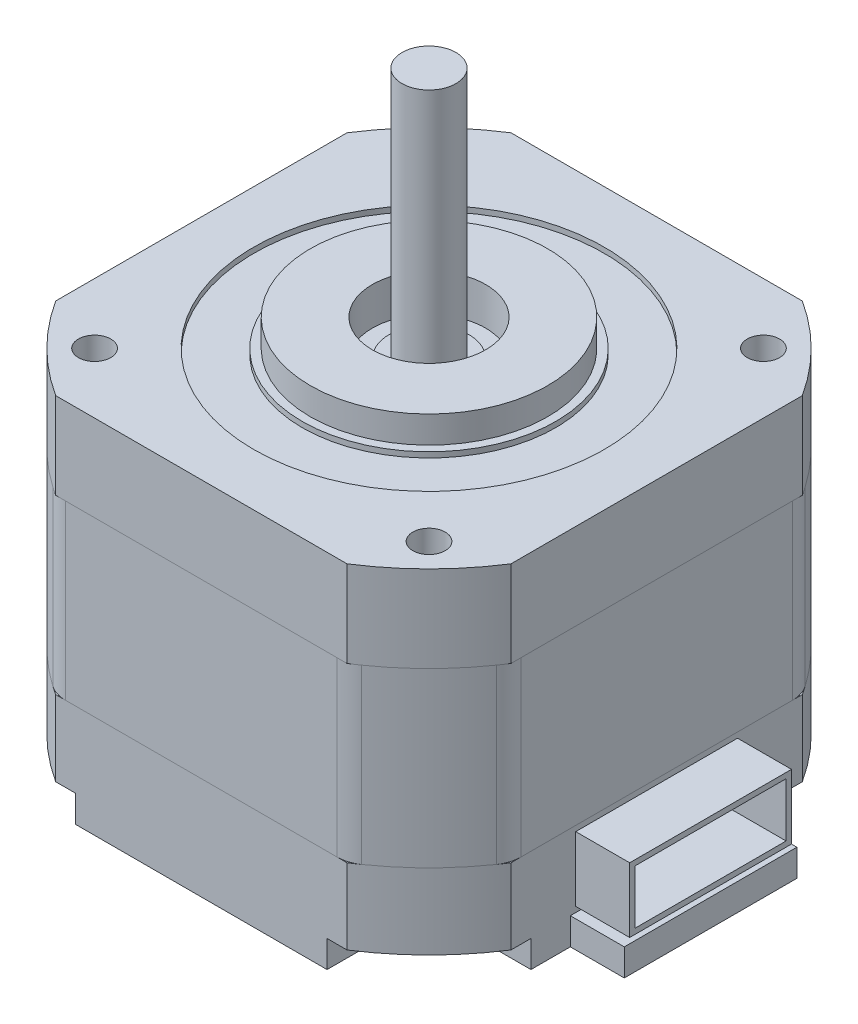
SolidWorks part; units mm, degrees
ref_plane "Alzado" through (0, 0, 0) normal (0, 0, 1) x (1, 0, 0)
ref_plane "Planta" through (0, 0, 0) normal (0, 1, 0) x (1, 0, 0)
ref_plane "Vista lateral" through (0, 0, 0) normal (1, 0, 0) x (0, 0, -1)
sketch "Croquis1" plane through (0, 0, 0) normal (0, 1, 0) x (1, 0, 0)
  line L0 (13.5, 21.1) -> (-13.5, 21.1)
  line L2 (-21.1, 13.5) -> (-21.1, -13.5)
  line L4 (-13.5, -21.1) -> (13.5, -21.1)
  line L6 (21.1, -13.5) -> (21.1, 13.5)
  arc A0 (-13.5, 21.1) -> (-21.1, 13.5) centre (0, 0) ccw
  arc A1 (13.5, 21.1) -> (21.1, 13.5) centre (0, 0) cw
  arc A2 (21.1, -13.5) -> (13.5, -21.1) centre (0, 0) cw
  arc A3 (-21.1, -13.5) -> (-13.5, -21.1) centre (0, 0) ccw
  point P4 (-21.1, 0)
  point P10 (0, 21.1)
  dimension "D2" = 27
  dimension "D1" = 42.2
extrude "Saliente-Extruir1" add sketch "Croquis1" along normal mid plane 16
sketch "Croquis2" plane through (0, 8, 0) normal (0, 1, 0) x (1, 0, 0)
  line L12 (13.5003, 21.101) -> (-13.5003, 21.101)
  line L13 (-21.101, 13.5003) -> (-21.101, -13.5003)
  line L14 (-13.5003, -21.101) -> (13.5003, -21.101)
  line L15 (21.101, -13.5003) -> (21.101, 13.5003)
  line L16 (13.5003, 21.101) -> (-13.5003, 21.101)
  line L17 (-21.101, 13.5003) -> (-21.101, -13.5003)
  line L18 (-13.5003, -21.101) -> (13.5003, -21.101)
  line L19 (21.101, -13.5003) -> (21.101, 13.5003)
  arc A12 (21.101, 13.5003) -> (13.5003, 21.101) centre (0, 0) ccw
  arc A13 (-13.5003, 21.101) -> (-21.101, 13.5003) centre (0, 0) ccw
  arc A14 (-21.101, -13.5003) -> (-13.5003, -21.101) centre (0, 0) ccw
  arc A15 (13.5003, -21.101) -> (21.101, -13.5003) centre (0, 0) ccw
  arc A16 (21.101, 13.5003) -> (13.5003, 21.101) centre (0, 0) ccw
  arc A17 (-13.5003, 21.101) -> (-21.101, 13.5003) centre (0, 0) ccw
  arc A18 (-21.101, -13.5003) -> (-13.5003, -21.101) centre (0, 0) ccw
  arc A19 (13.5003, -21.101) -> (21.101, -13.5003) centre (0, 0) ccw
  dimension "D1" = 0.001
fillet "Redondeo1" radius 3 8 edges at (-21.1, 0, -13.5) (-13.5, 0, -21.1) (13.5, 0, -21.1) (21.1, 0, -13.5) (-21.1, 0, 13.5) (-13.5, 0, 21.1) (13.5, 0, 21.1) (21.1, 0, 13.5)
extrude "Saliente-Extruir2" add sketch "Croquis2" along normal blind 8
sketch "Croquis3" plane through (0, -8, 0) normal (0, -1, 0) x (1, 0, 0)
  line L8 (-13.5003, -21.101) -> (13.5003, -21.101)
  line L9 (-21.101, 13.5003) -> (-21.101, -13.5003)
  line L10 (13.5003, 21.101) -> (-13.5003, 21.101)
  line L11 (21.101, -13.5003) -> (21.101, 13.5003)
  line L12 (-13.5003, -21.101) -> (13.5003, -21.101)
  line L13 (-21.101, 13.5003) -> (-21.101, -13.5003)
  line L14 (13.5003, 21.101) -> (-13.5003, 21.101)
  line L15 (21.101, -13.5003) -> (21.101, 13.5003)
  arc A8 (13.5003, -21.101) -> (21.101, -13.5003) centre (0, 0) ccw
  arc A9 (-21.101, -13.5003) -> (-13.5003, -21.101) centre (0, 0) ccw
  arc A10 (-13.5003, 21.101) -> (-21.101, 13.5003) centre (0, 0) ccw
  arc A11 (21.101, 13.5003) -> (13.5003, 21.101) centre (0, 0) ccw
  arc A12 (13.5003, -21.101) -> (21.101, -13.5003) centre (0, 0) ccw
  arc A13 (-21.101, -13.5003) -> (-13.5003, -21.101) centre (0, 0) ccw
  arc A14 (-13.5003, 21.101) -> (-21.101, 13.5003) centre (0, 0) ccw
  arc A15 (21.101, 13.5003) -> (13.5003, 21.101) centre (0, 0) ccw
  dimension "D1" = 0
extrude "Saliente-Extruir3" add sketch "Croquis3" along normal blind 9.5
sketch "Croquis4" plane through (0, 16, 0) normal (0, 1, 0) x (1, 0, 0)
  line L0 (-15.5, 15.5) -> (-15.5, 21.101) construction
  line L1 (-15.5, 15.5) -> (-21.101, 15.5) construction
  line L2 (-21.101, 13.5003) -> (-21.101, -13.5003) construction
  line L3 (13.5003, 21.101) -> (-13.5003, 21.101) construction
  line L4 (0, 0) -> (0, 21.101) construction
  line L5 (0, 0) -> (-21.101, 0) construction
  circle A0 centre (0, 0) radius 16.25
  circle A1 centre (0, 0) radius 11.75
  circle A2 centre (0, 0) radius 11
  circle A3 centre (-15.5, 15.5) radius 1.5
  circle A7 centre (-15.5, -15.5) radius 1.5
  circle A8 centre (15.5, -15.5) radius 1.5
  circle A9 centre (15.5, 15.5) radius 1.5
  dimension "D1" = 32.5
  dimension "D2" = 23.5
  dimension "D3" = 22
  dimension "D4" = 3
  dimension "D5" = 31
extrude "Cortar-Extruir1" cut sketch "Croquis4" against normal blind 0.5 contours A0 A1 region at (-15.7904, 16, 0)
extrude "Saliente-Extruir4" add sketch "Croquis4<3>" along normal blind 2.5 contours A2
sketch "Croquis4<3>" plane through (0, 16, 0) normal (0, 1, 0) x (1, 0, 0) same geometry as "Croquis4"
extrude "Cortar-Extruir2" cut sketch "Croquis4<4>" against normal blind 5.5 contours A3 | A9 | A8 | A7
sketch "Croquis4<4>" plane through (0, 16, 0) normal (0, 1, 0) x (1, 0, 0) same geometry as "Croquis4"
sketch "Croquis5" plane through (0, 18.5, 0) normal (0, 1, 0) x (1, 0, 0)
  circle A0 centre (0, 0) radius 5.25
  dimension "D1" = 10.5
extrude "Cortar-Extruir3" cut sketch "Croquis5" against normal blind 3.5
sketch "Croquis6" plane through (0, 15, 0) normal (0, 1, 0) x (1, 0, 0)
  circle A0 centre (0, 0) radius 2.5
  circle A1 centre (0, 0) radius 3.7
  dimension "D2" = 5
  dimension "D1" = 1.2
extrude "Saliente-Extruir5" add sketch "Croquis6" along normal blind 0.25
extrude "Saliente-Extruir6" add sketch "Croquis6<2>" along normal blind 23.5 contours A0 region at (0, 15, 0)
sketch "Croquis6<2>" plane through (0, 15, 0) normal (0, 1, 0) x (1, 0, 0) same geometry as "Croquis6"
sketch "Croquis7" plane through (0, -17.5, 0) normal (0, -1, 0) x (1, 0, 0)
  line L0 (-11.6503, 21.101) -> (-11.6503, 14.6503)
  line L1 (-21.101, 11.6503) -> (-14.6503, 11.6503)
  line L2 (-21.101, 0) -> (0, 0) construction
  line L3 (0, 0) -> (0, 21.101) construction
  line L4 (21.101, -13.5003) -> (21.101, 13.5003)
  line L5 (13.5003, 21.101) -> (-13.5003, 21.101)
  line L6 (-21.101, 13.5003) -> (-21.101, -13.5003)
  line L7 (-13.5003, -21.101) -> (13.5003, -21.101)
  line L9 (-11.6503, 21.101) -> (-13.5003, 21.101)
  line L10 (-21.101, 13.5003) -> (-21.101, 11.6503)
  line L12 (-21.101, 13.5003) -> (-21.101, -13.5003) construction
  line L13 (13.5003, 21.101) -> (-13.5003, 21.101) construction
  line L14 (-11.6503, -21.101) -> (-11.6503, -14.6503)
  line L15 (-21.101, -11.6503) -> (-14.6503, -11.6503)
  line L16 (-21.101, -13.5003) -> (-21.101, -11.6503)
  line L17 (-11.6503, -21.101) -> (-13.5003, -21.101)
  line L18 (11.6503, -21.101) -> (11.6503, -14.6503)
  line L19 (11.6503, -21.101) -> (13.5003, -21.101)
  line L20 (21.101, -13.5003) -> (21.101, -11.6503)
  line L21 (21.101, -11.6503) -> (14.6503, -11.6503)
  line L22 (11.6503, 21.101) -> (11.6503, 14.6503)
  line L23 (21.101, 11.6503) -> (14.6503, 11.6503)
  line L24 (21.101, 13.5003) -> (21.101, 11.6503)
  line L25 (11.6503, 21.101) -> (13.5003, 21.101)
  arc A0 (-11.6503, 14.6503) -> (-14.6503, 11.6503) centre (-14.6503, 14.6503) cw
  arc A1 (-11.6503, -14.6503) -> (-14.6503, -11.6503) centre (-14.6503, -14.6503) ccw
  arc A2 (-13.5003, -21.101) -> (-21.101, -13.5003) centre (0, 0) cw
  arc A3 (13.5003, -21.101) -> (21.101, -13.5003) centre (0, 0) ccw
  arc A4 (13.5003, -21.101) -> (21.101, -13.5003) centre (0, 0) ccw
  arc A5 (21.101, 13.5003) -> (13.5003, 21.101) centre (0, 0) ccw
  arc A6 (-13.5003, 21.101) -> (-21.101, 13.5003) centre (0, 0) ccw
  arc A7 (-21.101, -13.5003) -> (-13.5003, -21.101) centre (0, 0) ccw
  arc A10 (-13.5003, 21.101) -> (-21.101, 13.5003) centre (0, 0) ccw
  arc A12 (11.6503, -14.6503) -> (14.6503, -11.6503) centre (14.6503, -14.6503) cw
  arc A13 (11.6503, 14.6503) -> (14.6503, 11.6503) centre (14.6503, 14.6503) ccw
  arc A14 (13.5003, 21.101) -> (21.101, 13.5003) centre (0, 0) cw
  dimension "D3" = 3
  dimension "D2" = 1.85
  dimension "D1" = 0
extrude "Cortar-Extruir4" cut sketch "Croquis7" against normal blind 2.5
sketch "Croquis8" plane through (0, -15, 0) normal (0, -1, 0) x (1, 0, 0)
  circle A0 centre (15.5, -15.5) radius 1.5 construction
  circle A1 centre (-15.5, -15.5) radius 1.5 construction
  circle A2 centre (-15.5, 15.5) radius 1.5 construction
  circle A3 centre (15.5, 15.5) radius 1.5 construction
  circle A4 centre (15.5, -15.5) radius 1.5
  circle A5 centre (-15.5, -15.5) radius 1.5
  circle A6 centre (-15.5, 15.5) radius 1.5
  circle A7 centre (15.5, 15.5) radius 1.5
extrude "Cortar-Extruir5" cut sketch "Croquis8" against normal blind 15
sketch "Croquis9" plane through (0, -17.5, 0) normal (0, -1, 0) x (1, 0, 0)
  circle A2 centre (0, 0) radius 4.2
  circle A3 centre (0, 0) radius 4.2
  dimension "D1" = 0.5
extrude "Cortar-Extruir6" cut sketch "Croquis9" against normal blind 3
sketch "Croquis10" plane through (0, -14.5, 0) normal (0, -1, 0) x (1, 0, 0)
  circle A0 centre (0, 0) radius 2.5 construction
  circle A1 centre (0, 0) radius 3.7
  circle A2 centre (0, 0) radius 3.7
  circle A3 centre (0, 0) radius 2.5
  dimension "D1" = 0
extrude "Saliente-Extruir7" add sketch "Croquis10" along normal blind 0.25
extrude "Saliente-Extruir8" add sketch "Croquis10<2>" along normal blind 1.25 contours A3 region at (0, -14.5, 0)
sketch "Croquis10<2>" plane through (0, -14.5, 0) normal (0, -1, 0) x (1, 0, 0) same geometry as "Croquis10"
sketch "Croquis11" plane through (21.101, 0, 0) normal (1, 0, 0) x (0, 0, -1)
  line L0 (-12.5919, -8) -> (12.5919, -8) construction
  line L1 (8, -17.5) -> (-8, -17.5)
  line L2 (8, -17.5) -> (8, -15)
  line L3 (8, -15) -> (-8, -15)
  line L4 (-8, -17.5) -> (-8, -15)
  line L5 (-21.101, -15) -> (-13.5003, -15) construction
  line L6 (11.6503, -17.5) -> (-11.6503, -17.5) construction
  line L7 (8, -15) -> (-8, -15)
  line L8 (8, -15) -> (8, -8)
  line L9 (8, -8) -> (-8, -8)
  line L10 (-8, -15) -> (-8, -8)
  line L11 (7.5, -14.5) -> (7.5, -8.5)
  line L12 (7.5, -8.5) -> (-7.5, -8.5)
  line L13 (-7.5, -14.5) -> (-7.5, -8.5)
  line L14 (7.5, -14.5) -> (-7.5, -14.5)
  line L15 (7, -14) -> (7, -9)
  line L16 (7, -9) -> (-7, -9)
  line L17 (-7, -14) -> (-7, -9)
  line L18 (7, -14) -> (-7, -14)
  point P0 (0, -16.25)
  point P5 (0, -11.5)
  point P14 (0, -15)
  line M15 (-11.6503, -17.5) -> (11.6503, -17.5)
  dimension "D1" = 16
  dimension "D2" = 0.5
  dimension "D3" = 0.5
extrude "Saliente-Extruir9" add sketch "Croquis11" along normal blind 5 contours L14 L11 L12 L13 L15 L18 L17 L16 | L4 L2 L3 M15 region at (21.101, -16.25, 0) region at (21.101, -14.3384, 0)
